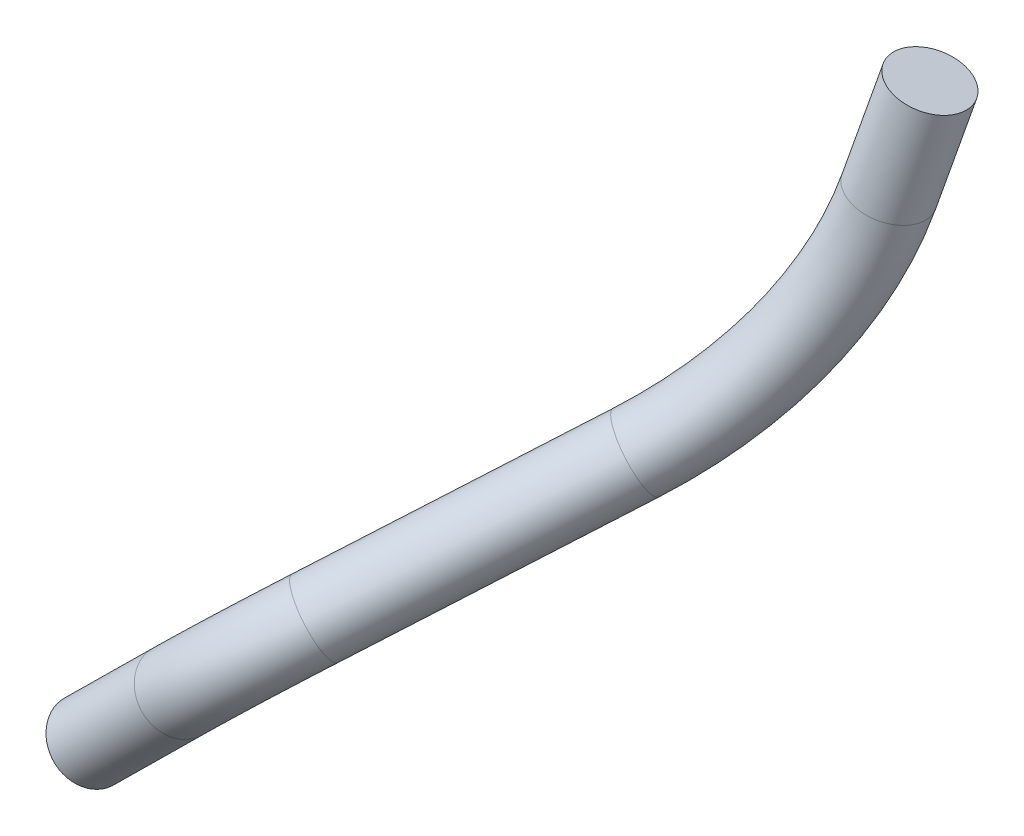
SolidWorks part; units mm, degrees
ref_plane "X-Y Datum" through (0, 0, 0) normal (0, 0, 1) x (1, 0, 0)
ref_plane "X-Z Datum" through (0, 0, 0) normal (0, 1, 0) x (1, 0, 0)
ref_plane "Y-Z Datum" through (0, 0, 0) normal (1, 0, 0) x (0, 0, -1)
sketch3d "3DSketch1"
  line L0 (249.9103, 151.4778, 165.0533) -> (253.6203, 165.14, 163.3218)
  line L1 (200.591, 91.8187, 210.3483) -> (188.8507, 80.2108, 210.3483)
  line L2 (212.6835, 103.2218, 204.1716) -> (232.5301, 120.7986, 181.3218)
  line L3 (195.6578, 87.5142, 210.3483) -> (196.2341, 86.9379, 210.3483) construction
  line L4 (214.5506, 105.7551, 201.8304) -> (214.8834, 104.2903, 201.8304) construction
  arc A1 (253.6579, 165.1264, 159.3218) -> (253.6579, 165.1264, 167.3218) centre (253.6579, 165.1264, 163.3218) ccw construction
  arc A2 (253.6203, 165.14, 168.0218) -> (253.6203, 165.14, 158.6218) centre (253.6203, 165.14, 163.3218) ccw construction
  arc A3 (232.5301, 120.7986, 181.3218) -> (249.9103, 151.4778, 165.0533) centre (222.3711, 164.1234, 205.8249) ccw
  arc A4 (212.6835, 103.2218, 204.1716) -> (200.591, 91.8187, 210.3483) centre (201.7257, 90.6711, 184.9996) ccw
  point P0 (198.0165, 89.2733, 210.3483)
  point P1 (253.6579, 165.1264, 163.3218)
  point P5 (207.3187, 98.4705, 210.3483)
  point P9 (252.2924, 161.3666, 163.3218)
  point P17 (252.0158, 160.7224, 163.3218)
  point P18 (244.4448, 131.3507, 167.6042)
  point P19 (262.9619, 156.8612, 235.4945)
  point P21 (195.9459, 87.226, 210.3483)
  point P22 (219.548, 72.6454, 186.6135)
  point P25 (195.9459, 87.226, 210.3483)
  point P26 (0, 0, 0)
  point P29 (214.717, 105.0227, 201.8304)
  point P30 (0, 0, 0)
  point P31 (0, 0, 0)
  point P32 (0, 0, 0)
  point P40 (214.717, 105.0227, 201.8304)
  dimension "D1" = 50.8
  dimension "D2" = 25.4
  dimension "D3" = 16.51
sweep "Sweep1" add path "3DSketch1" circular profile diameter 9.398 parameters "D3"=9.398
